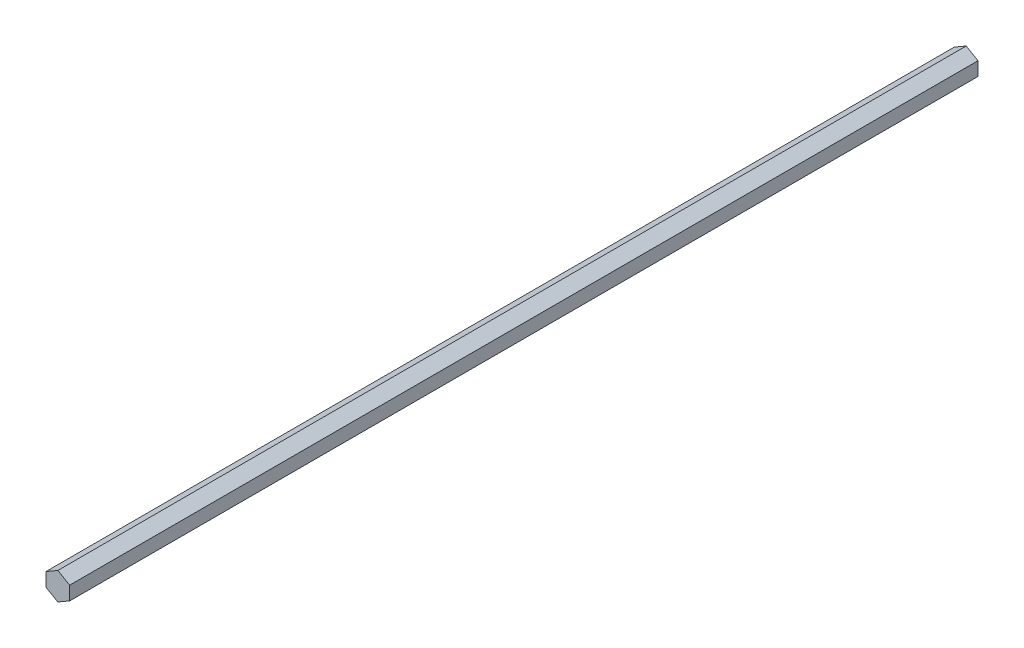
SolidWorks part; units mm, degrees
ref_plane "Front Plane" through (0, 0, 0) normal (0, 0, 1) x (1, 0, 0)
ref_plane "Top Plane" through (0, 0, 0) normal (0, 1, 0) x (1, 0, 0)
ref_plane "Right Plane" through (0, 0, 0) normal (1, 0, 0) x (0, 0, -1)
sketch "Sketch1" plane through (0, 0, 0) normal (0, 0, 1) x (1, 0, 0)
  line L0 (-6.35, 0) -> (6.35, 0) construction
  line L9 (0, 7.3323) -> (-6.35, 3.6662) construction
  line L10 (-6.35, 3.6662) -> (-6.35, -3.6662) construction
  line L11 (-6.35, -3.6662) -> (0, -7.3323) construction
  line L12 (0, -7.3323) -> (6.35, -3.6662) construction
  line L13 (6.35, -3.6662) -> (6.35, 3.6662) construction
  line L14 (6.35, 3.6662) -> (0, 7.3323) construction
  circle A3 centre (0, 0) radius 6.35 construction
  point P4 (0, 0)
  dimension "Width" = 12.7
sketch "Sketch2" plane through (0, 0, 0) normal (1, 0, 0) x (0, 0, -1)
  line L0 (243.84, 7.3323) -> (-243.84, 7.3323) construction
  point P3 (-229.235, 7.3323)
  point P4 (0, 7.3323)
  point P5 (229.235, 7.3323)
  dimension "Length" = 487.68
  dimension "D1" = 14.605
  dimension "D2" = 14.605
sketch "Sketch3" plane through (0, 0, 0) normal (0, 0, 1) x (1, 0, 0)
  line L1 (0, 7.3323) -> (6.35, 3.6662)
  line L2 (6.35, 3.6662) -> (6.35, -3.6662)
  line L3 (6.35, -3.6662) -> (0, -7.3323)
  line L4 (0, -7.3323) -> (-6.35, -3.6662)
  line L5 (-6.35, -3.6662) -> (-6.35, 3.6662)
  line L6 (-6.35, 3.6662) -> (0, 7.3323)
extrude "Boss-Extrude1" add sketch "Sketch3" along normal mid plane 487.68
equation "\"D1@Boss-Extrude1\" = \"Length@Sketch2\""
equation "\"D1@Sketch2\" = \"Width@Sketch1\" * 1.15"
equation "\"D2@Sketch2\"=\"D1@Sketch2\""
